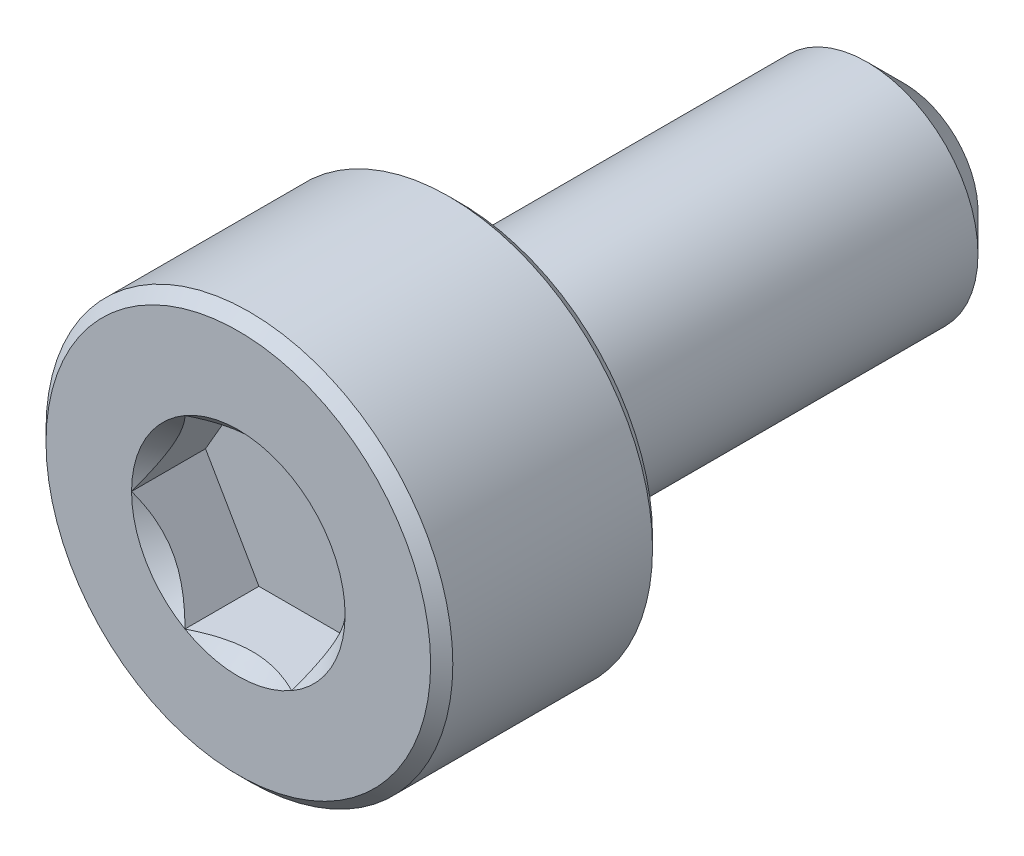
SolidWorks part; units mm, degrees
ref_plane "Front Plane" through (0, 0, 0) normal (0, 0, 1) x (1, 0, 0)
ref_plane "Top Plane" through (0, 0, 0) normal (0, 1, 0) x (1, 0, 0)
ref_plane "Right Plane" through (0, 0, 0) normal (1, 0, 0) x (0, 0, -1)
sketch "Sketch1" plane through (0, 0, 0) normal (1, 0, 0) x (0, 0, -1)
  line L0 (-4.5, 0) -> (4.5, 0) construction
  line L1 (4.5, 0) -> (4.5, 1) construction
  line L2 (4.5, 1) -> (4, 1.5) construction
  line L3 (4, 1.5) -> (-13.5, 1.5) construction
  line L5 (-1.5, 1.5) -> (-1.5, 2.75) construction
  line L6 (-1.5, 2.75) -> (-4.5, 2.75) construction
  line L7 (-4.5, 2.75) -> (-4.5, 0) construction
  line L8 (4.5, 1) -> (4.5, 1.5) construction
  line L9 (4.4688, 1.5541) -> (4.7187, 1.1211) construction
  line L10 (4.7187, 1.1211) -> (4.9687, 1.5541) construction
  line L11 (4.9687, 1.5541) -> (4.4688, 1.5541) construction
  line L12 (4.7188, 1.5541) -> (4.7187, 1.5) construction
  line L13 (4.7187, 1.1211) -> (4.7187, 1.1752) construction
  line L14 (4.6875, 1.1752) -> (4.75, 1.1752) construction
  line L15 (4.5, 1.5) -> (4.9375, 1.5) construction
  line L16 (4.4844, 1.5271) -> (4.9531, 1.5271) construction
  line L17 (4.5, 0) -> (4.5, -1.5) construction
  line L18 (-1.65, 2.75) -> (-1.5, 2.6) construction
  line L19 (-4.35, 2.75) -> (-4.5, 2.6) construction
  point P0 (-4.5, 1.25)
  point P3 (2.75, 1.5)
  point P4 (0, 0)
  point P22 (4.7187, 1.1752)
  point P24 (-13.5, 1.5)
  point P25 (4.7187, 1.5)
  point P28 (4.7188, 1.5271)
  point P29 (2.75, -1.5)
  point P31 (-3, 2.75)
  point P37 (-2.025, 2.75)
  point P38 (-4.275, 2.75)
  dimension "head height" = 3
  dimension "D1" = 45
  dimension "head dia" = 5.5
  dimension "thread dia" = 3
  dimension "drive size" = 2.5
  dimension "pitch" = 0.5
  dimension "D2" = 0.0625
  dimension "D3" = 0.5
  dimension "D4" = 1.75
  dimension "D7" = 0.15
  dimension "D8" = 0.15
  dimension "D9" = 0.15
  dimension "D10" = 0.075
  dimension "D11" = 0.375
  dimension "D12" = 18
  dimension "length" = 6
sketch "Sketch2" plane through (0, 0, 0) normal (1, 0, 0) x (0, 0, -1)
  line L1 (-4.35, 2.75) -> (-1.65, 2.75)
  line L4 (4, 1.5) -> (4.5, 1)
  line L5 (4.5, 1) -> (4.5, 0)
  line L6 (-1.65, 2.75) -> (-1.5, 2.6) construction
  line L7 (4.5, 0) -> (-4.5, 0)
  line L8 (-4.35, 2.75) -> (-4.5, 2.6) construction
  line L9 (-1.65, 2.75) -> (-1.5, 2.6)
  line L10 (-4.35, 2.75) -> (-4.5, 2.6)
  line L11 (-4.5, 2.6) -> (-4.5, 0)
  line L12 (-1.5, 2.6) -> (-1.5, 1.5)
  line L13 (-1.5, 1.5) -> (4, 1.5)
revolve "Revolve1" add sketch "Sketch2" angle 360 about L7
sketch "Sketch3" plane through (0, 0, 4.5) normal (0, 0, 1) x (1, 0, 0)
  line L1 (0.7217, 1.25) -> (-0.7217, 1.25)
  line L2 (-0.7217, 1.25) -> (-1.4434, 0)
  line L3 (-1.4434, 0) -> (-0.7217, -1.25)
  line L4 (-0.7217, -1.25) -> (0.7217, -1.25)
  line L5 (0.7217, -1.25) -> (1.4434, 0)
  line L6 (1.4434, 0) -> (0.7217, 1.25)
  circle A0 centre (0, 0) radius 1.25 construction
extrude "Cut-Extrude1" cut sketch "Sketch3" against normal offset from surface (1 mm away) 1 up to face at (-2.6, 0, 4.5)
sketch "Sketch4" plane through (0, 0, 4.5) normal (0, 0, 1) x (1, 0, 0)
  circle A0 centre (0, 0) radius 1.4434
extrude "Cut-Extrude2" cut sketch "Sketch4" against normal blind 0.5 draft 45
ref_plane "Plane1" [suppressed] through (0, 0, 13.5) normal (0, 0, 1) x (1, 0, 0)
split "Split1" [suppressed] bodies to split 106
sketch "Sketch6" [suppressed] plane through (0, 0, -4.5) normal (0, 0, -1) x (-1, 0, 0)
  circle A0 centre (0, 0) radius 1.5
curve "Helix/Spiral1" [suppressed] pitch 0.5 height 6.5 turns 13
sketch "Sketch7" [suppressed] plane through (0, 0, 0) normal (1, 0, 0) x (0, 0, -1)
  line L0 (4.4844, 1.5271) -> (4.9531, 1.5271)
  line L1 (4.9531, 1.5271) -> (4.75, 1.1752)
  line L2 (4.75, 1.1752) -> (4.6875, 1.1752)
  line L3 (4.6875, 1.1752) -> (4.4844, 1.5271)
sweep "Cut-Sweep1" [suppressed] cut profiles "Sketch7" path "Helix/Spiral1"
sketch "Sketch8" [suppressed] plane through (0, 0, 1.5) normal (0, 0, -1) x (-1, 0, 0)
  circle A0 centre (0, 0) radius 1.5
extrude "Boss-Extrude1" [suppressed] add sketch "Sketch8" along normal through all draft 45
ref_plane "Plane2" [suppressed] through (0, 0, 3) normal (0, 0, 1) x (1, 0, 0)
sketch "Sketch9" [suppressed] plane through (0, 0, 3) normal (0, 0, 1) x (1, 0, 0)
  line L0 (0, 2.6125) -> (0.048, 2.7496)
  line L1 (0, 2.6125) -> (-0.048, 2.7496)
  line L2 (0, 2.75) -> (0, 0) construction
  line L3 (-0.048, 2.7496) -> (0, 0) construction
  line L4 (0, 0) -> (0.048, 2.7496) construction
  arc A0 (0.048, 2.7496) -> (-0.048, 2.7496) centre (0, 0) ccw
  circle A1 centre (0, 0) radius 2.6125 construction
  dimension "D1" = 5.5
  dimension "D2" = 5.225
  dimension "D3" = 2
extrude "Cut-Extrude4" [suppressed] cut sketch "Sketch9" against normal up to vertex and the other way up to vertex
pattern_circular "CirPattern2" [suppressed] count 175 over 360 about axis through (0, 0, 4.5) along (0, 0, -1) of bodies 113
equation "\"D2@Sketch1\"=\"pitch@Sketch1\"/8"
equation "\"D3@Sketch1\"=\"pitch@Sketch1\""
equation "\"D3@Helix/Spiral1\"=\"length@Sketch1\"+\"pitch@Sketch1\""
equation "\"D4@Helix/Spiral1\"=\"pitch@Sketch1\""
equation "\"D4@Sketch1\"=\"pitch@Sketch1\"*3.5"
equation "\"D7@Sketch1\"=\"head height@Sketch1\"*.05"
equation "\"D8@Sketch1\"=\"D7@Sketch1\""
equation "\"D9@Sketch1\"=\"D7@Sketch1\""
equation "\"D10@Sketch1\"=\"D7@Sketch1\"/2"
equation "\"D11@Sketch1\"=\"D10@Sketch1\"*5"
equation "\"D2@Sketch9\"=\"D1@Sketch9\"*.95"
equation "\"D1@CirPattern2\"= ( 360 / \"D3@Sketch9\" ) - 5"
